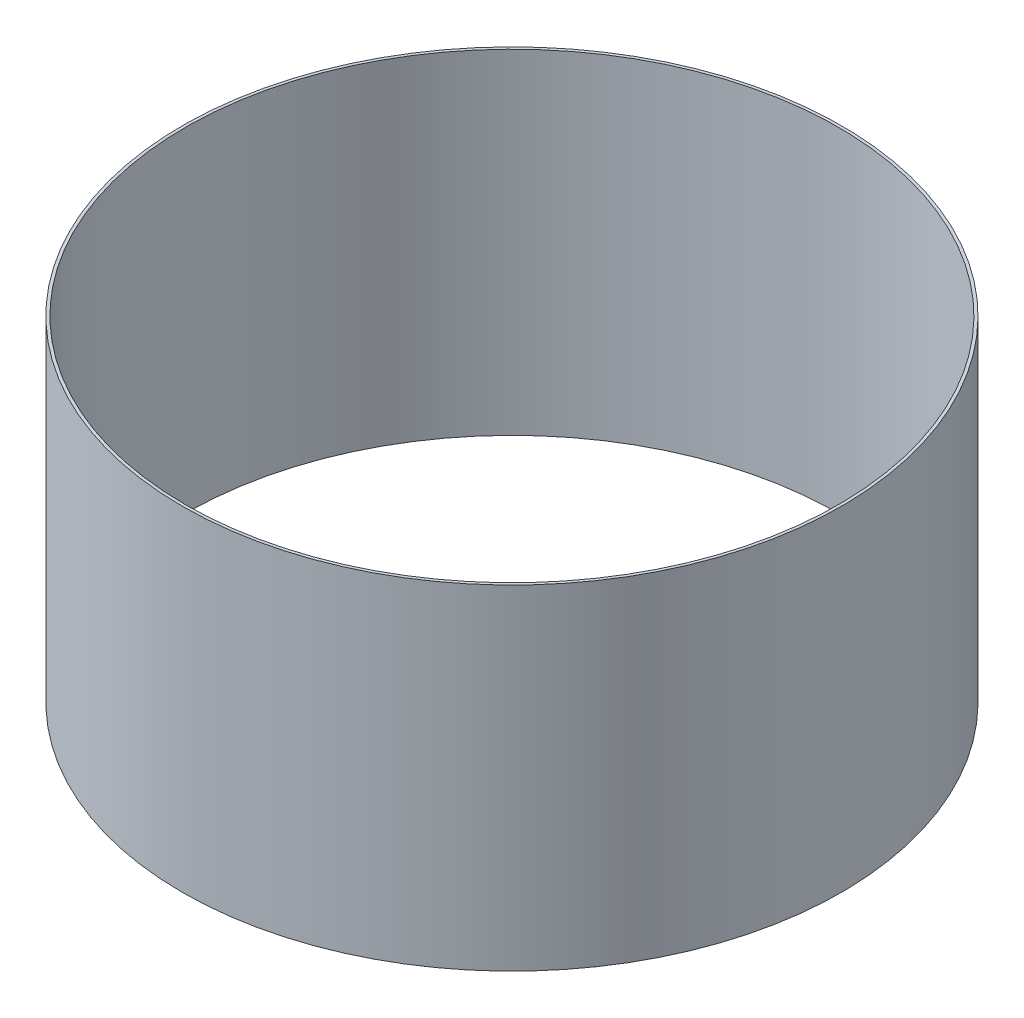
SolidWorks part; units mm, degrees
ref_plane "Front Plane" through (0, 0, 0) normal (0, 0, 1) x (1, 0, 0)
ref_plane "Top Plane" through (0, 0, 0) normal (0, 1, 0) x (1, 0, 0)
ref_plane "Right Plane" through (0, 0, 0) normal (1, 0, 0) x (0, 0, -1)
sketch "Sketch2" plane through (0, 0, 0) normal (0, 0, 1) x (1, 0, 0)
  line L0 (0, 64.0982) -> (0, -113.7018) construction
  line L1 (-175.2232, 64.0982) -> (-173.6992, 64.0982)
  line L2 (-175.2232, 64.0982) -> (-175.2232, -113.7018)
  line L3 (-175.2232, -113.7018) -> (-173.6992, -113.7018)
  line L4 (-173.6992, 64.0982) -> (-173.6992, -113.7018)
  dimension "D1" = 177.8
  dimension "D2" = 1.524
revolve "Revolve1" add sketch "Sketch2" angle 360 about L0
